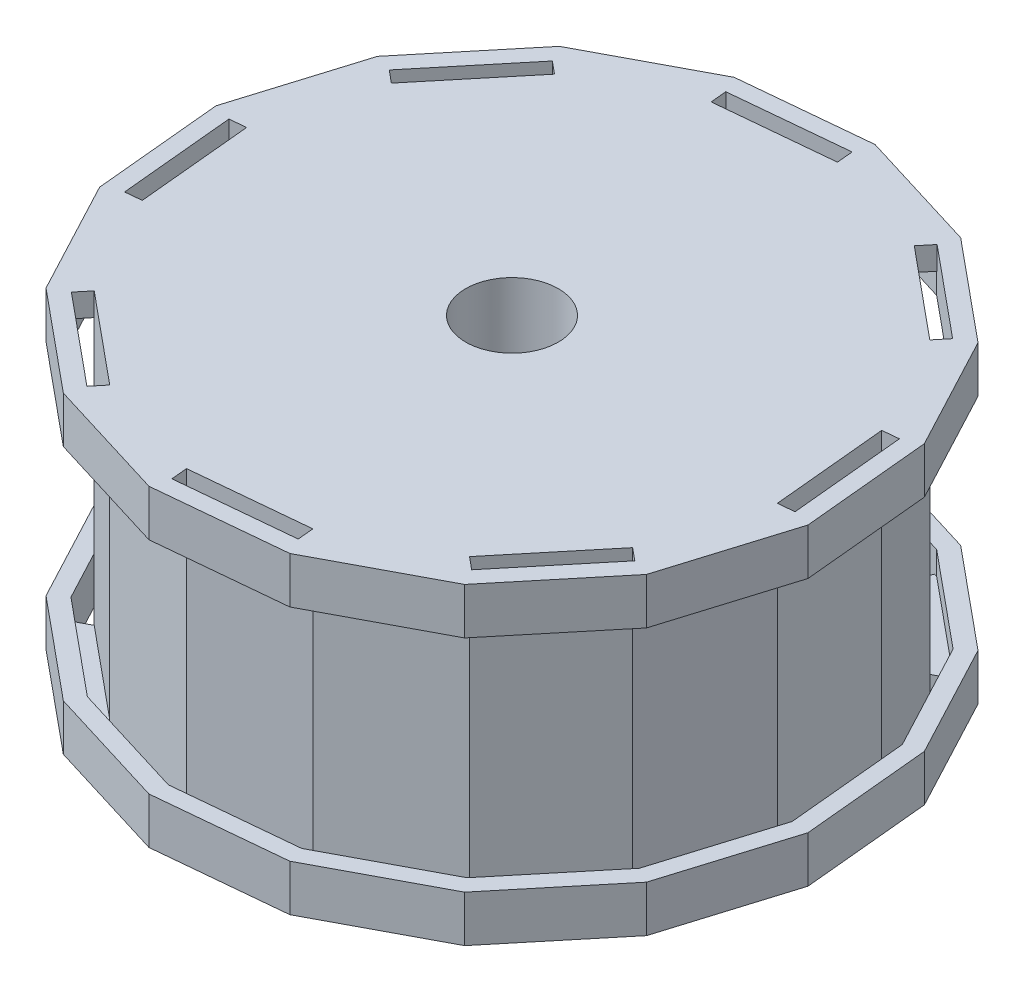
SolidWorks part; units mm, degrees
ref_plane "Front Plane" through (0, 0, 0) normal (0, 0, 1) x (1, 0, 0)
ref_plane "Top Plane" through (0, 0, 0) normal (0, 1, 0) x (1, 0, 0)
ref_plane "Right Plane" through (0, 0, 0) normal (1, 0, 0) x (0, 0, -1)
sketch "Sketch2" plane through (0, 0, 0) normal (0, 1, 0) x (1, 0, 0)
  line L0 (22.5639, -12.1542) -> (25.4975, -2.5942)
  line L1 (-24.5494, -7.3608) -> (-19.8638, -16.1951)
  line L2 (-19.8638, -16.1951) -> (-12.1542, -22.5639)
  line L3 (-12.1542, -22.5639) -> (-2.5942, -25.4975)
  line L4 (-2.5942, -25.4975) -> (7.3608, -24.5494)
  line L5 (7.3608, -24.5494) -> (16.1951, -19.8638)
  line L6 (16.1951, -19.8638) -> (22.5639, -12.1542)
  line L7 (25.4975, -2.5942) -> (24.5494, 7.3608)
  line L8 (24.5494, 7.3608) -> (19.8638, 16.1951)
  line L9 (19.8638, 16.1951) -> (12.1542, 22.5639)
  line L10 (12.1542, 22.5639) -> (2.5942, 25.4975)
  line L11 (2.5942, 25.4975) -> (-7.3608, 24.5494)
  line L12 (-7.3608, 24.5494) -> (-16.1951, 19.8638)
  line L13 (-16.1951, 19.8638) -> (-22.5639, 12.1542)
  line L14 (-22.5639, 12.1542) -> (-25.4975, 2.5942)
  line L15 (-25.4975, 2.5942) -> (-24.5494, -7.3608)
  circle A0 centre (0, 0) radius 25.1367 construction
  dimension "D1" = 10
extrude "Boss-Extrude1" add sketch "Sketch2" along normal blind 27
sketch "Sketch3" plane through (0, 27, 0) normal (0, 1, 0) x (1, 0, 0)
  line L0 (-7.3608, 24.5494) -> (2.5942, 25.4975)
  line L1 (2.5942, 25.4975) -> (2.4615, 26.8912)
  line L2 (2.4615, 26.8912) -> (-7.4935, 25.9431)
  line L3 (-7.4935, 25.9431) -> (-7.3608, 24.5494)
  line L4 (-2.3833, 25.0235) -> (-7.3608, 24.5494)
  line L5 (0, 0) -> (-7.3608, 24.5494)
  line L6 (-3.3997, 11.3386) -> (-4.1529, 13.8505)
  line L7 (-4.2488, 26.2521) -> (-7.7707, 25.9167)
  line L8 (0, 0) -> (-5.0601, 16.8763)
  line L9 (-7.7707, 25.9167) -> (-17.0971, 20.9702)
  line L10 (-17.0971, 20.9702) -> (-23.8206, 12.8311)
  line L11 (-23.8206, 12.8311) -> (-26.9176, 2.7387)
  line L12 (-26.9176, 2.7387) -> (-25.9167, -7.7707)
  line L13 (-25.9167, -7.7707) -> (-20.9702, -17.0971)
  line L14 (-20.9702, -17.0971) -> (-12.8311, -23.8206)
  line L15 (-12.8311, -23.8206) -> (-2.7387, -26.9176)
  line L16 (-2.7387, -26.9176) -> (7.7707, -25.9167)
  line L17 (7.7707, -25.9167) -> (17.0971, -20.9702)
  line L18 (17.0971, -20.9702) -> (23.8206, -12.8311)
  line L19 (23.8206, -12.8311) -> (26.9176, -2.7387)
  line L20 (26.9176, -2.7387) -> (25.9167, 7.7707)
  line L21 (25.9167, 7.7707) -> (20.9702, 17.0971)
  line L22 (20.9702, 17.0971) -> (12.8311, 23.8206)
  line L23 (12.8311, 23.8206) -> (2.7387, 26.9176)
  line L24 (2.7387, 26.9176) -> (-7.7707, 25.9167)
  line L25 (3.0049, 26.8359) -> (2.5942, 25.4975)
  line L26 (-8.21, 27.3816) -> (-18.0635, 22.1555)
  line L27 (-18.0635, 22.1555) -> (-25.1671, 13.5564)
  line L28 (-25.1671, 13.5564) -> (-28.4392, 2.8935)
  line L29 (-28.4392, 2.8935) -> (-27.3816, -8.21)
  line L30 (-27.3816, -8.21) -> (-22.1555, -18.0635)
  line L31 (-22.1555, -18.0635) -> (-13.5564, -25.1671)
  line L32 (-13.5564, -25.1671) -> (-2.8935, -28.4392)
  line L33 (-2.8935, -28.4392) -> (8.21, -27.3816)
  line L34 (8.21, -27.3816) -> (18.0635, -22.1555)
  line L35 (18.0635, -22.1555) -> (25.1671, -13.5564)
  line L36 (25.1671, -13.5564) -> (28.4392, -2.8935)
  line L37 (28.4392, -2.8935) -> (27.3816, 8.21)
  line L38 (27.3816, 8.21) -> (22.1555, 18.0635)
  line L39 (22.1555, 18.0635) -> (13.5564, 25.1671)
  line L40 (13.5564, 25.1671) -> (2.8935, 28.4392)
  line L41 (2.8935, 28.4392) -> (-8.21, 27.3816)
  line L42 (2.5942, 25.4975) -> (12.1542, 22.5639)
  line L43 (12.1542, 22.5639) -> (12.5649, 23.9023)
  line L44 (12.5649, 23.9023) -> (3.0049, 26.8359)
  line L45 (13.0458, 23.6432) -> (12.1542, 22.5639)
  line L46 (12.1542, 22.5639) -> (19.8638, 16.1951)
  line L47 (19.8638, 16.1951) -> (20.7555, 17.2744)
  line L48 (20.7555, 17.2744) -> (13.0458, 23.6432)
  line L49 (21.1007, 16.8511) -> (19.8638, 16.1951)
  line L50 (19.8638, 16.1951) -> (24.5494, 7.3608)
  line L51 (24.5494, 7.3608) -> (25.7862, 8.0167)
  line L52 (25.7862, 8.0167) -> (21.1007, 16.8511)
  line L53 (25.9431, 7.4935) -> (24.5494, 7.3608)
  line L54 (24.5494, 7.3608) -> (25.4975, -2.5942)
  line L55 (25.4975, -2.5942) -> (26.8912, -2.4615)
  line L56 (26.8912, -2.4615) -> (25.9431, 7.4935)
  line L57 (26.8359, -3.0049) -> (25.4975, -2.5942)
  line L58 (25.4975, -2.5942) -> (22.5639, -12.1542)
  line L59 (22.5639, -12.1542) -> (23.9023, -12.5649)
  line L60 (23.9023, -12.5649) -> (26.8359, -3.0049)
  line L61 (23.6432, -13.0458) -> (22.5639, -12.1542)
  line L62 (22.5639, -12.1542) -> (16.1951, -19.8638)
  line L63 (16.1951, -19.8638) -> (17.2744, -20.7555)
  line L64 (17.2744, -20.7555) -> (23.6432, -13.0458)
  line L65 (16.8511, -21.1007) -> (16.1951, -19.8638)
  line L66 (16.1951, -19.8638) -> (7.3608, -24.5494)
  line L67 (7.3608, -24.5494) -> (8.0167, -25.7862)
  line L68 (8.0167, -25.7862) -> (16.8511, -21.1007)
  line L69 (7.4935, -25.9431) -> (7.3608, -24.5494)
  line L70 (7.3608, -24.5494) -> (-2.5942, -25.4975)
  line L71 (-2.5942, -25.4975) -> (-2.4615, -26.8912)
  line L72 (-2.4615, -26.8912) -> (7.4935, -25.9431)
  line L73 (-3.0049, -26.8359) -> (-2.5942, -25.4975)
  line L74 (-2.5942, -25.4975) -> (-12.1542, -22.5639)
  line L75 (-12.1542, -22.5639) -> (-12.5649, -23.9023)
  line L76 (-12.5649, -23.9023) -> (-3.0049, -26.8359)
  line L77 (-13.0458, -23.6432) -> (-12.1542, -22.5639)
  line L78 (-12.1542, -22.5639) -> (-19.8638, -16.1951)
  line L79 (-19.8638, -16.1951) -> (-20.7555, -17.2744)
  line L80 (-20.7555, -17.2744) -> (-13.0458, -23.6432)
  line L81 (-21.1007, -16.8511) -> (-19.8638, -16.1951)
  line L82 (-19.8638, -16.1951) -> (-24.5494, -7.3608)
  line L83 (-24.5494, -7.3608) -> (-25.7862, -8.0167)
  line L84 (-25.7862, -8.0167) -> (-21.1007, -16.8511)
  line L85 (-25.9431, -7.4935) -> (-24.5494, -7.3608)
  line L86 (-24.5494, -7.3608) -> (-25.4975, 2.5942)
  line L87 (-25.4975, 2.5942) -> (-26.8912, 2.4615)
  line L88 (-26.8912, 2.4615) -> (-25.9431, -7.4935)
  line L89 (-26.8359, 3.0049) -> (-25.4975, 2.5942)
  line L90 (-25.4975, 2.5942) -> (-22.5639, 12.1542)
  line L91 (-22.5639, 12.1542) -> (-23.9023, 12.5649)
  line L92 (-23.9023, 12.5649) -> (-26.8359, 3.0049)
  line L93 (-23.6432, 13.0458) -> (-22.5639, 12.1542)
  line L94 (-22.5639, 12.1542) -> (-16.1951, 19.8638)
  line L95 (-16.1951, 19.8638) -> (-17.2744, 20.7555)
  line L96 (-17.2744, 20.7555) -> (-23.6432, 13.0458)
  line L97 (-16.8511, 21.1007) -> (-16.1951, 19.8638)
  line L98 (-16.1951, 19.8638) -> (-7.3608, 24.5494)
  line L99 (-7.3608, 24.5494) -> (-8.0167, 25.7862)
  line L100 (-8.0167, 25.7862) -> (-16.8511, 21.1007)
  circle A0 centre (0, 0) radius 26.5367 construction
  circle A1 centre (0, 0) radius 28.0367 construction
  point P110 (0, 0)
  line M37 (-25.4975, 2.5942) -> (-24.5494, -7.3608)
  line M38 (-24.5494, -7.3608) -> (-19.8638, -16.1951)
  line M39 (-19.8638, -16.1951) -> (-12.1542, -22.5639)
  line M40 (-12.1542, -22.5639) -> (-2.5942, -25.4975)
  line M41 (-2.5942, -25.4975) -> (7.3608, -24.5494)
  line M42 (7.3608, -24.5494) -> (16.1951, -19.8638)
  line M43 (16.1951, -19.8638) -> (22.5639, -12.1542)
  line M44 (22.5639, -12.1542) -> (25.4975, -2.5942)
  line M45 (25.4975, -2.5942) -> (24.5494, 7.3608)
  line M46 (24.5494, 7.3608) -> (19.8638, 16.1951)
  line M47 (19.8638, 16.1951) -> (12.1542, 22.5639)
  line M48 (12.1542, 22.5639) -> (2.5942, 25.4975)
  line M49 (2.5942, 25.4975) -> (-7.3608, 24.5494)
  line M50 (-7.3608, 24.5494) -> (-16.1951, 19.8638)
  line M51 (-16.1951, 19.8638) -> (-22.5639, 12.1542)
  line M52 (-22.5639, 12.1542) -> (-25.4975, 2.5942)
  dimension "D1" = 1.4
  dimension "D2" = 1.5
  dimension "D3" = 16
extrude "Boss-Extrude2" add sketch "Sketch3" against normal blind 2 separate body contours L79 L14 L77 M39 | L87 L12 L85 M37 | L95 L10 L93 M51 | L2 L3 L0 L1 M49 | L47 L22 L45 M47 | L55 L20 L53 M45 | L63 L18 L61 M43 | L71 L16 L69 M41 | L28 L29 L30 L31 L32 L33 L34 L35 L36 L37 L38 L39 L40 L41 L26 L27 region at (-2.4497, 27, -25.7203) region at (-19.9192, 27, -16.4548) region at (16.4548, 27, -19.9192) region at (-25.7203, 27, 2.4497) region at (25.7203, 27, -2.4497) region at (-16.4548, 27, 19.9192) region at (19.9192, 27, 16.4548) region at (2.4497, 27, 25.7203)
sketch "Sketch4" plane through (0, 0, 0) normal (0, -1, 0) x (-1, 0, 0)
  line L4 (-12.1542, 22.5639) -> (-2.5942, 25.4975) construction
  line L5 (-2.8935, 28.4392) -> (-13.5564, 25.1671)
  line L6 (-13.5564, 25.1671) -> (-22.1555, 18.0635)
  line L7 (-22.1555, 18.0635) -> (-27.3816, 8.21)
  line L8 (-27.3816, 8.21) -> (-28.4392, -2.8935)
  line L101 (-28.4392, -2.8935) -> (-25.1671, -13.5564)
  line L102 (-25.1671, -13.5564) -> (-18.0635, -22.1555)
  line L103 (-18.0635, -22.1555) -> (-8.21, -27.3816)
  line L104 (-8.21, -27.3816) -> (2.8935, -28.4392)
  line L105 (2.8935, -28.4392) -> (13.5564, -25.1671)
  line L106 (13.5564, -25.1671) -> (22.1555, -18.0635)
  line L107 (22.1555, -18.0635) -> (27.3816, -8.21)
  line L108 (27.3816, -8.21) -> (28.4392, 2.8935)
  line L109 (28.4392, 2.8935) -> (25.1671, 13.5564)
  line L110 (25.1671, 13.5564) -> (18.0635, 22.1555)
  line L111 (18.0635, 22.1555) -> (8.21, 27.3816)
  line L112 (8.21, 27.3816) -> (-2.8935, 28.4392)
  line L113 (-2.5942, 25.4975) -> (-12.1542, 22.5639)
  line L114 (-12.1542, 22.5639) -> (-19.8638, 16.1951)
  line L115 (-19.8638, 16.1951) -> (-24.5494, 7.3608)
  line L116 (-24.5494, 7.3608) -> (-25.4975, -2.5942)
  line L117 (-25.4975, -2.5942) -> (-22.5639, -12.1542)
  line L118 (-22.5639, -12.1542) -> (-16.1951, -19.8638)
  line L119 (-16.1951, -19.8638) -> (-7.3608, -24.5494)
  line L120 (-7.3608, -24.5494) -> (2.5942, -25.4975)
  line L121 (2.5942, -25.4975) -> (12.1542, -22.5639)
  line L122 (12.1542, -22.5639) -> (19.8638, -16.1951)
  line L123 (19.8638, -16.1951) -> (24.5494, -7.3608)
  line L124 (24.5494, -7.3608) -> (25.4975, 2.5942)
  line L125 (25.4975, 2.5942) -> (22.5639, 12.1542)
  line L126 (22.5639, 12.1542) -> (16.1951, 19.8638)
  line L127 (16.1951, 19.8638) -> (7.3608, 24.5494)
  line L128 (7.3608, 24.5494) -> (-2.5942, 25.4975)
  line L129 (-12.8311, 23.8206) -> (-20.9702, 17.0971)
  line L130 (-20.9702, 17.0971) -> (-25.9167, 7.7707)
  line L131 (-25.9167, 7.7707) -> (-26.9176, -2.7387)
  line L132 (-26.9176, -2.7387) -> (-23.8206, -12.8311)
  line L133 (-23.8206, -12.8311) -> (-17.0971, -20.9702)
  line L134 (-17.0971, -20.9702) -> (-7.7707, -25.9167)
  line L135 (-7.7707, -25.9167) -> (2.7387, -26.9176)
  line L136 (2.7387, -26.9176) -> (12.8311, -23.8206)
  line L137 (12.8311, -23.8206) -> (20.9702, -17.0971)
  line L138 (20.9702, -17.0971) -> (25.9167, -7.7707)
  line L139 (25.9167, -7.7707) -> (26.9176, 2.7387)
  line L140 (26.9176, 2.7387) -> (23.8206, 12.8311)
  line L141 (23.8206, 12.8311) -> (17.0971, 20.9702)
  line L142 (17.0971, 20.9702) -> (7.7707, 25.9167)
  line L143 (7.7707, 25.9167) -> (-2.7387, 26.9176)
  line L144 (-2.7387, 26.9176) -> (-12.8311, 23.8206)
  line L145 (-2.4615, 26.8912) -> (7.4935, 25.9431) construction
  line L146 (-2.8935, 28.4392) -> (8.21, 27.3816) construction
  circle A0 centre (0, 0) radius 28.0367 construction
  circle A1 centre (0, 0) radius 25.1367 construction
  circle A2 centre (0, 0) radius 26.5367 construction
  line M120 (24.5494, -7.3608) -> (25.4975, 2.5942)
  line M121 (25.4975, 2.5942) -> (22.5639, 12.1542)
  line M122 (22.5639, 12.1542) -> (16.1951, 19.8638)
  line M123 (16.1951, 19.8638) -> (7.3608, 24.5494)
  line M124 (7.3608, 24.5494) -> (-2.5942, 25.4975)
  line M125 (-2.5942, 25.4975) -> (-12.1542, 22.5639)
  line M126 (-12.1542, 22.5639) -> (-19.8638, 16.1951)
  line M127 (-19.8638, 16.1951) -> (-24.5494, 7.3608)
  line M128 (-24.5494, 7.3608) -> (-25.4975, -2.5942)
  line M129 (-25.4975, -2.5942) -> (-22.5639, -12.1542)
  line M130 (-22.5639, -12.1542) -> (-16.1951, -19.8638)
  line M131 (-16.1951, -19.8638) -> (-7.3608, -24.5494)
  line M132 (-7.3608, -24.5494) -> (2.5942, -25.4975)
  line M133 (2.5942, -25.4975) -> (12.1542, -22.5639)
  line M134 (12.1542, -22.5639) -> (19.8638, -16.1951)
  line M135 (19.8638, -16.1951) -> (24.5494, -7.3608)
  dimension "D1" = 0
  dimension "D2" = 0
  dimension "D3" = 0
extrude "Boss-Extrude3" add sketch "Sketch4" against normal blind 4 separate body contours L111 L112 L5 L6 L7 L8 L101 L102 L103 L104 L105 L106 L107 L108 L109 L110 L144 L143 L142 L141 L140 L139 L138 L137 L136 L135 L134 L133 L132 L131 L130 L129 region at (-2.582, 0, -27.1096)
extrude "Boss-Extrude4" add sketch "Sketch4<4>" against normal blind 2 contours L143 L144 L129 L130 L131 L132 L133 L134 L135 L136 L137 L138 L139 L140 L141 L142 M120 M135 M134 M133 M132 M131 M130 M129 M128 M127 M126 M125 M124 M123 M122 M121 region at (7.5616, 0, -24.6413)
sketch "Sketch4<4>" plane through (0, 0, 0) normal (0, -1, 0) x (-1, 0, 0) same geometry as "Sketch4"
extrude "Cut-Extrude1" cut sketch "Sketch3<3>" against normal through all both and the other way through all contours L91 L11 L89 M52 | L99 L9 L97 M50 | L43 L23 L25 M48 | L51 L21 L49 M46 | L59 L19 L57 M44 | L67 L17 L65 M42 | L75 L15 L73 M40 | L83 L13 L81 M38 region at (-12.1059, 27, -22.825) region at (7.5796, 27, -24.6999) region at (-24.6999, 27, -7.5796) region at (22.825, 27, -12.1059) region at (-22.825, 27, 12.1059) region at (24.6999, 27, 7.5796) region at (-7.5796, 27, 24.6999) region at (12.1059, 27, 22.825)
sketch "Sketch3<3>" plane through (0, 27, 0) normal (0, 1, 0) x (1, 0, 0) same geometry as "Sketch3"
extrude "Boss-Extrude8" add sketch "Sketch3<5>" against normal blind 2 contours L99 L9 L97 M50 | L43 L23 L25 M48 | L51 L21 L49 M46 | L59 L19 L57 M44 | L67 L17 L65 M42 | L75 L15 L73 M40 | L83 L13 L81 M38 | L91 L11 L89 M52 region at (-12.1059, 27, -22.825) region at (7.5796, 27, -24.6999) region at (-24.6999, 27, -7.5796) region at (22.825, 27, -12.1059) region at (-22.825, 27, 12.1059) region at (24.6999, 27, 7.5796) region at (-7.5796, 27, 24.6999) region at (12.1059, 27, 22.825)
sketch "Sketch3<5>" plane through (0, 27, 0) normal (0, 1, 0) x (1, 0, 0) same geometry as "Sketch3"
extrude "Boss-Extrude9" add sketch "Sketch3<6>" against normal blind 4 contours L40 L41 L26 L27 L28 L29 L30 L31 L32 L33 L34 L35 L36 L37 L38 L39 L24 L23 L22 L21 L20 L19 L18 L17 L16 L15 L14 L13 region at (-2.582, 27, -27.1096)
sketch "Sketch3<6>" plane through (0, 27, 0) normal (0, 1, 0) x (1, 0, 0) same geometry as "Sketch3"
sketch "Sketch5" plane through (0, 0, 0) normal (0, -1, 0) x (1, 0, 0)
  circle A0 centre (0, 0) radius 4
  dimension "D1" = 8
extrude "Cut-Extrude2" cut sketch "Sketch5" against normal through all both and the other way through all
